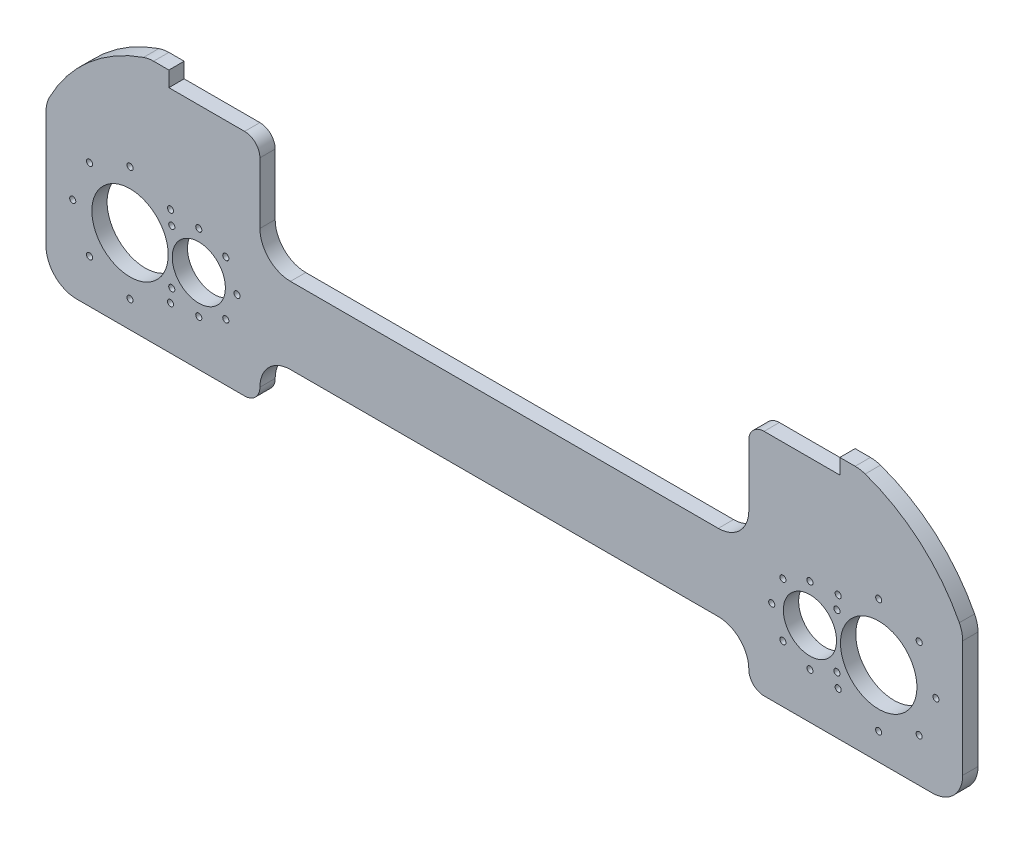
SolidWorks part; units mm, degrees
material "ABS"
ref_plane "Front Plane" through (0, 0, 0) normal (0, 0, 1) x (1, 0, 0)
ref_plane "Top Plane" through (0, 0, 0) normal (0, 1, 0) x (1, 0, 0)
ref_plane "Right Plane" through (0, 0, 0) normal (1, 0, 0) x (0, 0, -1)
sketch "Sketch1" plane through (0, 0, 0) normal (0, 0, 1) x (1, 0, 0)
  line L0 (-145.7836, 66.675) -> (145.7836, 66.675)
  line L1 (-190.5, 26.1817) -> (-190.5, -22.225)
  line L4 (0, 0) -> (0, 100.7987) construction
  line L5 (-177.8, -34.925) -> (177.8, -34.925)
  line L6 (190.5, 26.1817) -> (190.5, -22.225)
  line L7 (-190.5, 34.925) -> (190.5, -34.925) construction
  line L8 (-190.5, -34.925) -> (190.5, 34.925) construction
  arc A0 (177.8, -34.925) -> (190.5, -22.225) centre (177.8, -22.225) ccw
  arc A1 (149.9577, 65.9694) -> (189.0889, 31.9999) centre (127, 0) cw
  circle A2 centre (-127, 0) radius 3.175
  circle A3 centre (127, 0) radius 3.175
  arc A4 (-177.8, -34.925) -> (-190.5, -22.225) centre (-177.8, -22.225) cw
  arc A5 (190.5, 26.1817) -> (189.0889, 31.9999) centre (177.8, 26.1817) ccw
  arc A6 (-149.9577, 65.9694) -> (-189.0889, 31.9999) centre (-127, 0) ccw
  arc A7 (149.9577, 65.9694) -> (145.7836, 66.675) centre (145.7836, 53.975) ccw
  arc A8 (-190.5, 26.1817) -> (-189.0889, 31.9999) centre (-177.8, 26.1817) cw
  arc A9 (-145.7836, 66.675) -> (-149.9577, 65.9694) centre (-145.7836, 53.975) ccw
  point P0 (0, 0)
  point P22 (190.5, 29.0994)
  point P27 (147.8199, 66.675)
  point P30 (-190.5, 29.0994)
  point P33 (-147.8199, 66.675)
  dimension "D3" = 6.35
  dimension "D4" = 6.35
  dimension "D6" = 66.675
  dimension "D7" = 12.7
  dimension "D2" = 381
  dimension "D5" = 12.7
  dimension "D1" = 69.85
  dimension "D8" = 139.7
extrude "Boss-Extrude1" add sketch "Sketch1" along normal mid plane 6.35
sketch "Sketch2" plane through (0, 0, 3.175) normal (0, 0, 1) x (1, 0, 0)
  line L0 (-127, 0) -> (-207.737, 0) construction
  line L4 (0, 0) -> (0, 93.9723) construction
  circle A0 centre (-127, 0) radius 11.049
  circle A1 centre (-155.575, 0) radius 15.875
  circle A2 centre (127, 0) radius 15.875 construction
  circle A3 centre (155.575, 0) radius 23.8125 construction
  circle A4 centre (-155.575, 0) radius 23.8125 construction
  circle A5 centre (-127, 0) radius 15.875 construction
  circle A6 centre (-155.575, 23.8125) radius 1.27
  circle A7 centre (-138.737, 16.838) radius 1.27
  circle A8 centre (-131.7625, 0) radius 1.27 [skipped]
  circle A9 centre (-138.737, -16.838) radius 1.27
  circle A10 centre (-155.575, -23.8125) radius 1.27
  circle A11 centre (-172.413, -16.838) radius 1.27
  circle A12 centre (-179.3875, 0) radius 1.27
  circle A13 centre (-172.413, 16.838) radius 1.27
  circle A14 centre (-127, 15.875) radius 1.27
  circle A15 centre (-115.7747, 11.2253) radius 1.27
  circle A16 centre (-111.125, 0) radius 1.27
  circle A17 centre (-115.7747, -11.2253) radius 1.27
  circle A18 centre (-127, -15.875) radius 1.27
  circle A19 centre (-138.2253, -11.2253) radius 1.27
  circle A20 centre (138.2253, 11.2253) radius 1.27
  circle A21 centre (-138.2253, 11.2253) radius 1.27
  circle A22 centre (-142.875, 0) radius 1.27 [skipped]
  circle A23 centre (138.2253, -11.2253) radius 1.27
  circle A24 centre (127, -15.875) radius 1.27
  circle A25 centre (115.7747, -11.2253) radius 1.27
  circle A26 centre (111.125, 0) radius 1.27
  circle A27 centre (115.7747, 11.2253) radius 1.27
  circle A28 centre (127, 15.875) radius 1.27
  circle A29 centre (172.413, 16.838) radius 1.27
  circle A30 centre (179.3875, 0) radius 1.27
  circle A31 centre (172.413, -16.838) radius 1.27
  circle A32 centre (155.575, -23.8125) radius 1.27
  circle A33 centre (138.737, -16.838) radius 1.27
  circle A34 centre (138.737, 16.838) radius 1.27
  circle A35 centre (155.575, 23.8125) radius 1.27
  circle A36 centre (155.575, 0) radius 15.875
  circle A37 centre (127, 0) radius 11.049
  dimension "D2" = 28.575
  dimension "D3" = 31.75
  dimension "D4" = 31.75
  dimension "D5" = 47.625
  dimension "D6" = 2.54
  dimension "D1" = 22.098
  dimension "D8" = 2.54
  dimension "D7" = 8
  dimension "D9" = 8
extrude "Cut-Extrude1" cut sketch "Sketch2" against normal through all
sketch "Sketch5" plane through (0, 0, 3.175) normal (0, 0, 1) x (1, 0, 0)
  line L0 (145.7836, 66.675) -> (-145.7836, 66.675) construction
  line L1 (-88.9, 15.875) -> (88.9, 15.875)
  line L2 (-101.6, 28.575) -> (-101.6, 66.675)
  line L3 (-101.6, 66.675) -> (101.6, 66.675)
  line L4 (101.6, 28.575) -> (101.6, 66.675)
  line L5 (-101.6, 15.875) -> (101.6, 66.675) construction
  line L6 (-101.6, 66.675) -> (101.6, 15.875) construction
  line L7 (0, 0) -> (0, 128.2224) construction
  arc A0 (101.6, 28.575) -> (88.9, 15.875) centre (88.9, 28.575) cw
  arc A1 (-88.9, 15.875) -> (-101.6, 28.575) centre (-88.9, 28.575) cw
  point P0 (0, 41.275)
  dimension "D3" = 12.7
  dimension "D1" = 50.8
  dimension "D2" = 203.2
extrude "ITC_Cutout" cut sketch "Sketch5" against normal through all
sketch "Sketch6" plane through (0, 0, 3.175) normal (0, 0, 1) x (1, 0, 0)
  line L0 (-101.6, 66.675) -> (-145.7836, 66.675) construction
  line L1 (-71.9103, 66.675) -> (-139.4336, 66.675)
  line L2 (-71.9103, 66.675) -> (-71.9103, 60.325)
  line L3 (-71.9103, 60.325) -> (-139.4336, 60.325)
  line L4 (-139.4336, 66.675) -> (-139.4336, 60.325)
  line L5 (0, 0) -> (0, 132.6418) construction
  line L6 (139.4336, 66.675) -> (139.4336, 60.325)
  line L7 (71.9103, 60.325) -> (139.4336, 60.325)
  line L8 (71.9103, 66.675) -> (71.9103, 60.325)
  line L9 (71.9103, 66.675) -> (139.4336, 66.675)
  dimension "D1" = 6.35
  dimension "D2" = 6.35
extrude "Cut-Extrude3" cut sketch "Sketch6" against normal through all
fillet "Fillet1" radius 6.35 2 edges at (101.6, 60.325, 0) (-101.6, 60.325, 0)
sketch "Sketch7" plane through (0, 0, 3.175) normal (0, 0, 1) x (1, 0, 0)
  line L0 (0, 38.9819) -> (0, -79.3414) construction
  line L1 (-177.8, -34.925) -> (177.8, -34.925) construction
  line L2 (-88.9, -15.875) -> (88.9, -15.875)
  line L3 (-101.6, -28.575) -> (-101.6, -34.925)
  line L4 (-101.6, -34.925) -> (101.6, -34.925)
  line L5 (101.6, -28.575) -> (101.6, -34.925)
  line L6 (-101.6, -15.875) -> (101.6, -34.925) construction
  line L7 (-101.6, -34.925) -> (101.6, -15.875) construction
  line L8 (-101.6, 53.975) -> (-101.6, 28.575) construction
  arc A0 (101.6, -28.575) -> (88.9, -15.875) centre (88.9, -28.575) ccw
  arc A1 (-88.9, -15.875) -> (-101.6, -28.575) centre (-88.9, -28.575) ccw
  point P3 (0, -25.4)
  dimension "D2" = 12.7
  dimension "D1" = 19.05
extrude "Cut-Extrude4" cut sketch "Sketch7" against normal through all
fillet "Fillet2" radius 6.35 2 edges at (101.6, -34.925, 0) (-101.6, -34.925, 0)
